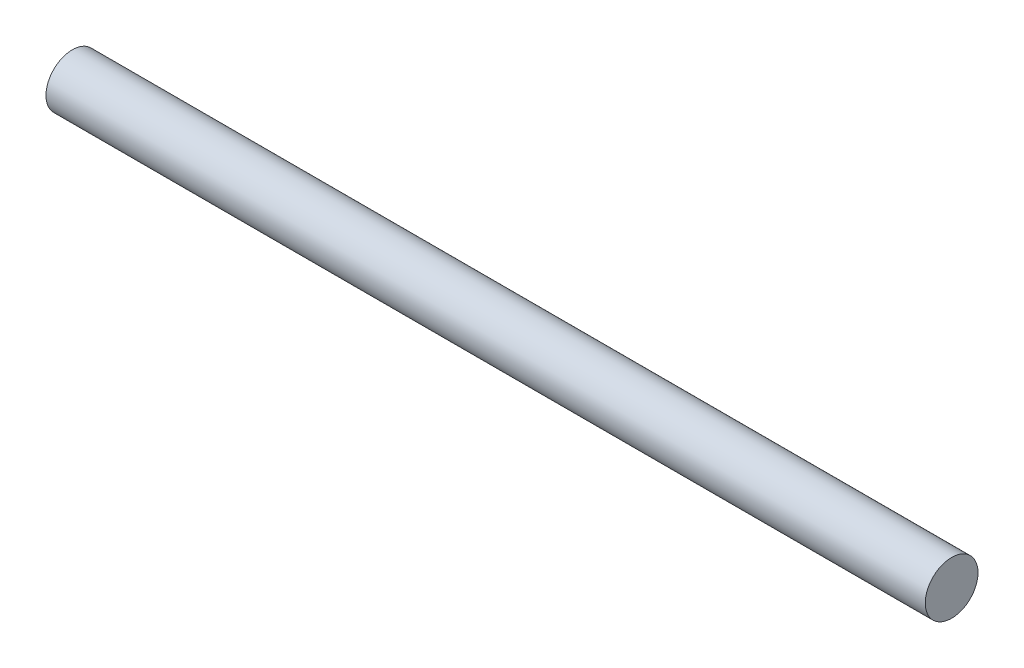
SolidWorks part; units mm, degrees
material "2014 Alloy"
ref_plane "Front Plane" through (0, 0, 0) normal (0, 0, 1) x (1, 0, 0)
ref_plane "Top Plane" through (0, 0, 0) normal (0, 1, 0) x (1, 0, 0)
ref_plane "Right Plane" through (0, 0, 0) normal (1, 0, 0) x (0, 0, -1)
sketch "Sketch1" plane through (0, 0, 0) normal (1, 0, 0) x (0, 0, -1)
  circle A0 centre (0, 0) radius 1.5
  dimension "D1" = 3
extrude "Extrude1" add sketch "Sketch1" along normal blind 25 and the other way blind 25
